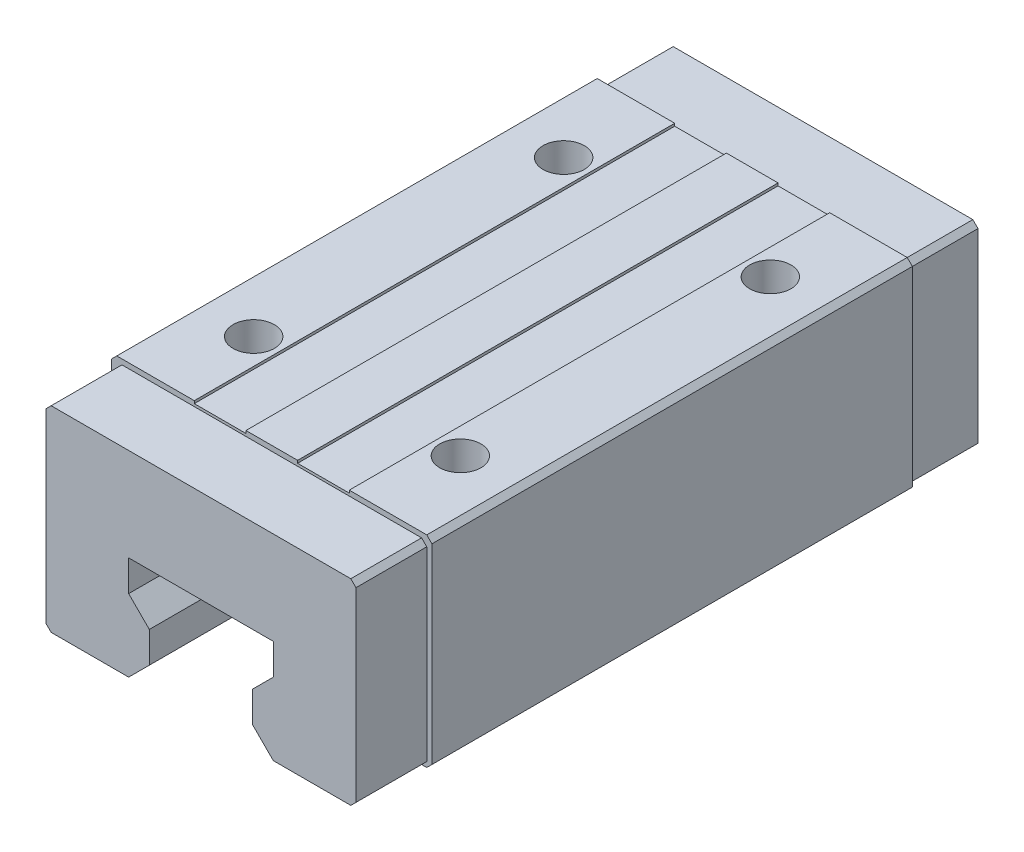
SolidWorks part; units mm, degrees
ref_plane "前视基准面" through (0, 0, 0) normal (0, 0, 1) x (1, 0, 0)
ref_plane "上视基准面" through (0, 0, 0) normal (0, 1, 0) x (1, 0, 0)
ref_plane "右视基准面" through (0, 0, 0) normal (1, 0, 0) x (0, 0, -1)
other "Configuration Table"
sketch "草图1" plane through (0, 0, 0) normal (0, 0, 1) x (1, 0, 0)
  line L0 (0, 55.4366) -> (0, -12.6403) construction
  line L1 (-30, 38) -> (30, 38)
  line L2 (30, 38) -> (30, 0)
  line L3 (30, 0) -> (14, 0)
  line L8 (14, 20) -> (-14, 20)
  line L13 (-30, 0) -> (-14, 0)
  line L14 (-30, 38) -> (-30, 0)
  line L15 (14, 14) -> (10, 10)
  line L16 (10, 10) -> (10, 4)
  line L17 (10, 4) -> (14, 0)
  line L19 (-10, 4) -> (-14, 0)
  line L20 (-10, 10) -> (-10, 4)
  line L21 (-14, 14) -> (-10, 10)
  line L22 (14, 14) -> (14, 20)
  line L23 (-14, 14) -> (-14, 20)
  point P16 (0, 0)
  point P17 (14.195, -0.195)
  point P19 (0, 20)
  point P25 (0, 38)
  dimension "D1" = 38
  dimension "D2" = 30
  dimension "D3" = 14
  dimension "D4" = 20
  dimension "D5" = 6
  dimension "D6" = 135
  dimension "D7" = 6
  dimension "D8" = 4
extrude "凸台-拉伸1" add sketch "草图1" along normal blind 120.4 contours L17 L3 L2 L1 L14 L13 L19 L20 L21 L23 L8 L22 L15 L16
ref_plane "基准面1" through (0, 0, 60.2) normal (0, 0, 1) x (1, 0, 0)
sketch "草图2" plane through (0, 0, 60.2) normal (0, 0, 1) x (1, 0, 0)
  line L0 (-31, 0) -> (-30, 0)
  line L1 (-30, 38) -> (-30, 0) construction
  line L2 (-31, 0) -> (-31, 39)
  line L3 (-31, 39) -> (-15, 39)
  line L4 (-30, 38) -> (30, 38) construction
  line L6 (-5, 39) -> (5, 39)
  line L7 (0, 0) -> (0, 45.4303) construction
  line L8 (31, 0) -> (30, 0)
  line L11 (-30, 38) -> (30, 38)
  line L12 (-30, 38) -> (-30, 0)
  line L13 (-15, 39) -> (-15, 38.5)
  line L14 (-15, 38.5) -> (-5, 38.5)
  line L15 (-5, 38.5) -> (-5, 39)
  line L16 (5, 38.5) -> (5, 39)
  line L17 (15, 38.5) -> (5, 38.5)
  line L18 (15, 39) -> (15, 38.5)
  line L19 (30, 38) -> (30, 0)
  line L20 (31, 39) -> (15, 39)
  line L21 (31, 0) -> (31, 39)
  line L22 (31, 0) -> (30, 0)
  point P8 (0, 39)
  point P10 (0, 39)
  point P13 (0, 39)
  point P23 (0, 38)
  dimension "D1" = 1
  dimension "D2" = 1
  dimension "D3" = 5
  dimension "D4" = 10
  dimension "D5" = 0.5
extrude "凸台-拉伸2" add sketch "草图2" along normal mid plane 93 contours L19 L11 L12 L0 L2 L3 L13 L14 L15 L6 L16 L17 L18 L20 L21 L8
sketch "草图4" plane through (0, 39, 0) normal (0, 1, 0) x (1, 0, 0)
  line L0 (0, 0) -> (0, -127.4396) construction
  line L1 (-42.8685, -60.2) -> (57.3984, -60.2) construction
  line L2 (-30, -120.4) -> (30, -120.4) construction
  line L3 (-30, 0) -> (30, 0) construction
  circle A0 centre (20, -30.2) radius 4
  circle A1 centre (20, -90.2) radius 4
  circle A2 centre (-20, -90.2) radius 4
  circle A3 centre (-20, -30.2) radius 4
  dimension "D1" = 8
  dimension "D2" = 20
  dimension "D3" = 60
extrude "切除-拉伸1" cut sketch "草图4" against normal blind 10
chamfer "倒角1" distance 1 angle 45 12 edges at (30, 0, 113.55) (31, 0, 60.2) (30, 0, 6.85) (-30, 38, 6.85) (30, 38, 6.85) (31, 39, 60.2) (30, 38, 113.55) (-31, 39, 60.2) (-30, 38, 113.55) (-30, 0, 6.85) (-30, 0, 113.55) (-31, 0, 60.2)
